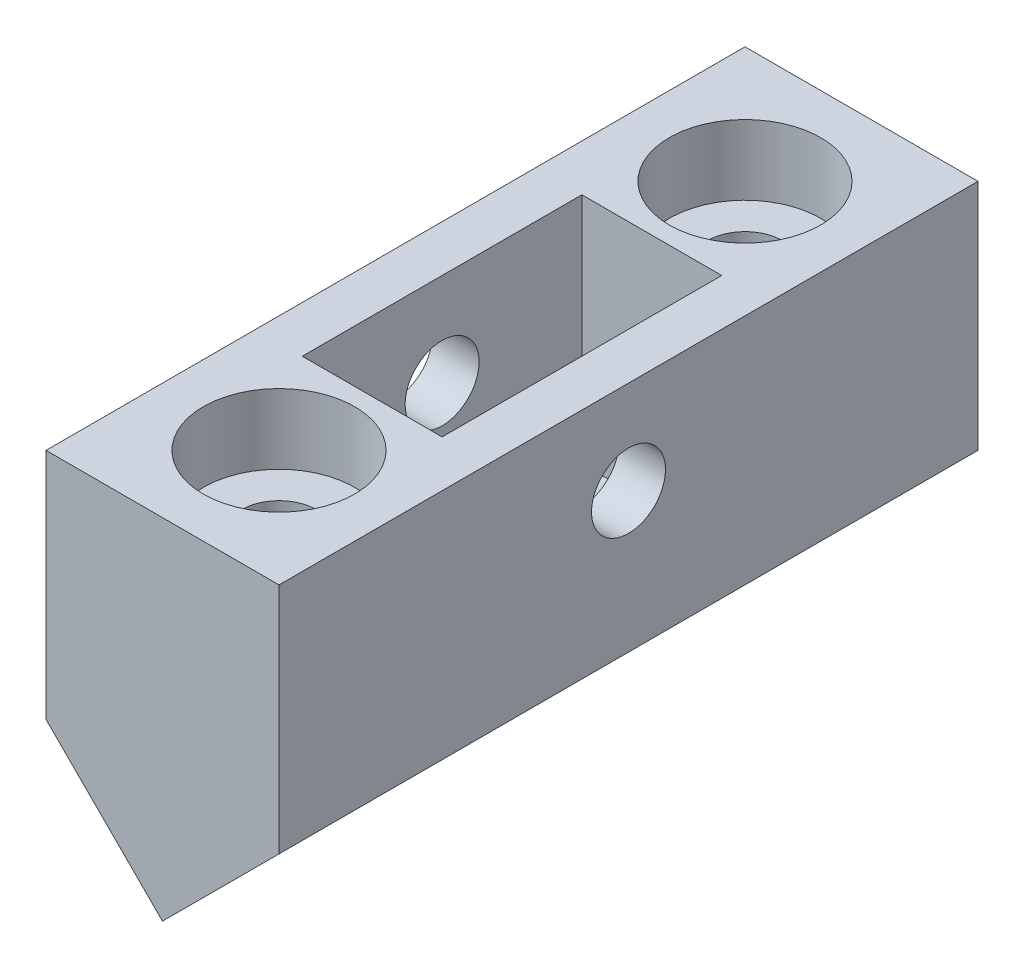
SolidWorks part; units mm, degrees
ref_plane "Front Plane" through (0, 0, 0) normal (0, 0, 1) x (1, 0, 0)
ref_plane "Top Plane" through (0, 0, 0) normal (0, 1, 0) x (1, 0, 0)
ref_plane "Right Plane" through (0, 0, 0) normal (1, 0, 0) x (0, 0, -1)
sketch "Sketch1" plane through (0, 0, 0) normal (0, 0, 1) x (1, 0, 0)
  line L0 (0, 5) -> (0, -56.5295) construction
  line L1 (-5, 5) -> (5, 5)
  line L2 (-5, 5) -> (-5, -5)
  line L4 (5, 5) -> (5, -5)
  line L5 (-5, 5) -> (5, -5) construction
  line L6 (-5, -5) -> (5, 5) construction
  line L7 (-5, -5) -> (0, -10)
  line L8 (0, -10) -> (5, -5)
  point P0 (0, 0)
  dimension "D1" = 90
  dimension "D2" = 10
  dimension "D3" = 10
extrude "Boss-Extrude1" add sketch "Sketch1" along normal blind 15 and the other way blind 15
sketch "Sketch2" plane through (0, 5, 0) normal (0, 1, 0) x (1, 0, 0)
  line L1 (-3, 6) -> (3, 6)
  line L2 (-3, 6) -> (-3, -6)
  line L3 (-3, -6) -> (3, -6)
  line L4 (3, 6) -> (3, -6)
  line L5 (-3, 6) -> (3, -6) construction
  line L6 (-3, -6) -> (3, 6) construction
  point P0 (0, 0)
  dimension "D1" = 6
  dimension "D2" = 12
extrude "Cut-Extrude1" cut sketch "Sketch2" against normal blind 10
sketch "Sketch3" plane through (5, 0, 0) normal (1, 0, 0) x (0, 0, -1)
  line L0 (0, 0) -> (0, 5) construction
  line L1 (15, 5) -> (-15, 5) construction
  circle A0 centre (0, 1) radius 1.5875
  point P7 (0, 2)
  dimension "D1" = 3.175
  dimension "D2" = 4
extrude "Cut-Extrude2" cut sketch "Sketch3" against normal through all
hole_wizard "CBORE for M3 SHCS1" positions "Sketch4" profile "Sketch5" counterbore size "M3" standard "ANSI Metric" end condition through all
sketch "Sketch4" plane through (0, 5, 0) normal (0, 1, 0) x (1, 0, 0)
  line L0 (5, 0) -> (-5, 0) construction
  line L1 (5, 15) -> (5, -15) construction
  line L2 (-5, 15) -> (-5, -15) construction
  line L4 (0, -15) -> (0, 15) construction
  line L5 (5, -15) -> (-5, -15) construction
  line L6 (5, 15) -> (-5, 15) construction
  point P0 (0, -10)
  point P20 (0, 10)
  dimension "D1" = 20
sketch "Sketch5" plane through (0, 5, 10) normal (1, 0, 0) x (0, 0, 1)
  line L0 (0, 0) -> (0, 15)
  line L1 (0, 15) -> (1.6, 15)
  line L3 (1.6, 15) -> (1.6, 3)
  line L4 (1.6, 3) -> (3.25, 3)
  line L5 (3.25, 3) -> (3.25, 0)
  line L7 (3.25, 0) -> (0, 0)
  line L11 (0, -6.35) -> (0, 107.95) construction
  dimension "Thru Hole Dia." = 3.2
  dimension "Thru Hole Depth" = 15
  dimension "C'Bore Dia." = 6.5
  dimension "C'Bore Depth" = 3
